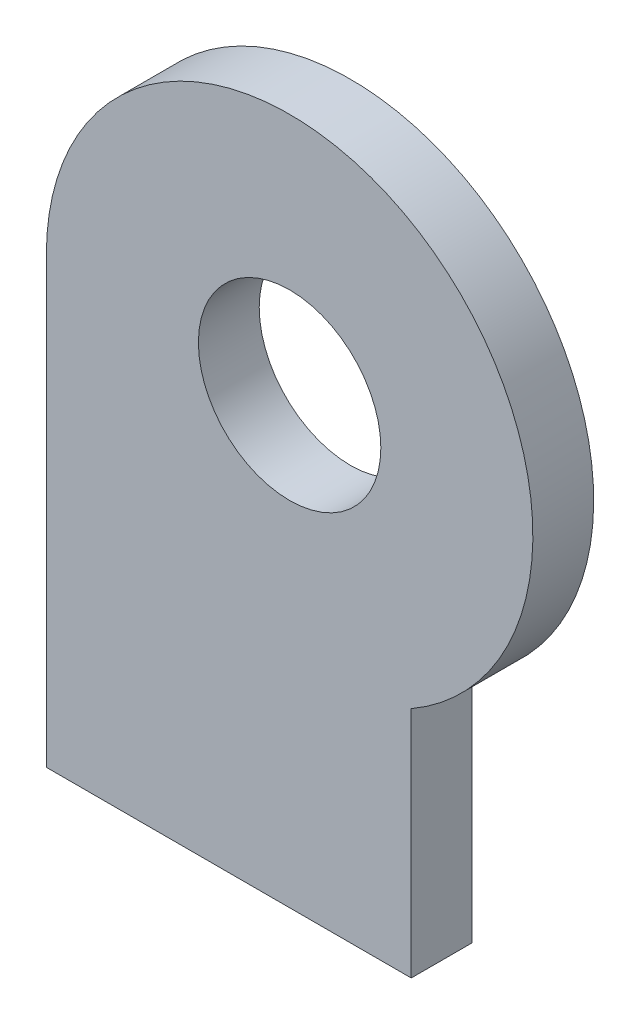
SolidWorks part; units mm, degrees
ref_plane "Front Plane" through (0, 0, 0) normal (0, 0, 1) x (1, 0, 0)
ref_plane "Top Plane" through (0, 0, 0) normal (0, 1, 0) x (1, 0, 0)
ref_plane "Right Plane" through (0, 0, 0) normal (1, 0, 0) x (0, 0, -1)
sketch "Sketch1" plane through (0, 0, 0) normal (0, 0, 1) x (1, 0, 0)
  line L0 (7.9877, -2.8207) -> (20.6877, -2.8207) construction
  line L1 (20.6877, -2.8207) -> (20.6877, 20.3568) construction
  line L2 (20.6877, 20.3568) -> (20.6877, 33.0568) construction
  line L3 (20.6877, 20.3568) -> (15.9252, 20.3568) construction
  line L5 (7.9877, 20.3568) -> (7.9877, -2.8207)
  line L12 (33.2915, 21.9172) -> (33.2915, 0) construction
  line L13 (7.9877, -2.8207) -> (27.0377, -2.8207)
  line L14 (27.0377, -2.8207) -> (27.0377, 9.3583)
  circle A0 centre (20.6877, 20.3568) radius 4.7625
  arc A10 (27.0377, 9.3583) -> (7.9877, 20.3568) centre (20.6877, 20.3568) ccw
  arc A11 (27.0377, 9.3583) -> (20.6877, 7.6568) centre (20.6877, 20.3568) ccw construction
  dimension "D2" = 9.525
  dimension "D4" = 19.05
  dimension "D1" = 23.1775
extrude "Boss-Extrude1" add sketch "Sketch1" along normal blind 3.175
